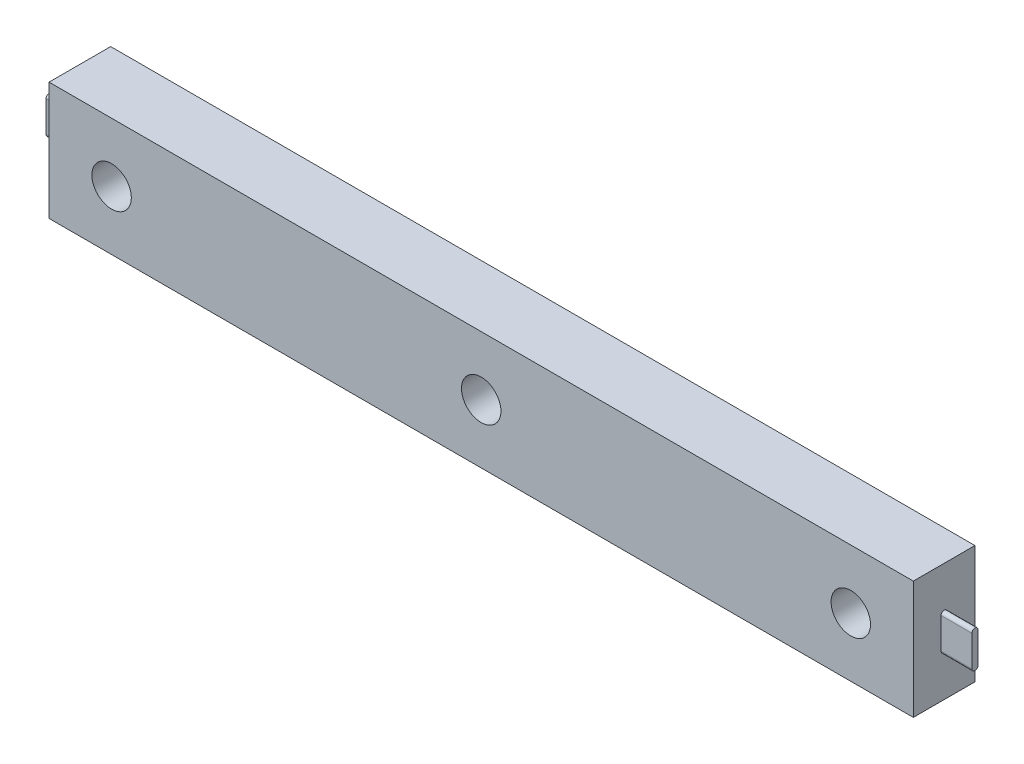
SolidWorks part; units mm, degrees
ref_plane "Front Plane" through (0, 0, 0) normal (0, 0, 1) x (1, 0, 0)
ref_plane "Top Plane" through (0, 0, 0) normal (0, 1, 0) x (1, 0, 0)
ref_plane "Right Plane" through (0, 0, 0) normal (1, 0, 0) x (0, 0, -1)
sketch "Sketch1" plane through (0, 0, 0) normal (0, 0, 1) x (1, 0, 0)
  line L1 (-89.093, -12.1729) -> (89.093, -12.1729)
  line L2 (-89.093, -12.1729) -> (-89.093, 12.1729)
  line L3 (-89.093, 12.1729) -> (89.093, 12.1729)
  line L4 (89.093, -12.1729) -> (89.093, 12.1729)
  line L5 (-89.093, -12.1729) -> (89.093, 12.1729) construction
  line L6 (-89.093, 12.1729) -> (89.093, -12.1729) construction
  circle A0 centre (0, 0) radius 4.064
  circle A1 centre (-76.2, 0) radius 4.064
  circle A2 centre (76.2, 0) radius 4.064
  point P0 (0, 0)
  dimension "D1" = 8.128
  dimension "D2" = 8.128
  dimension "D3" = 8.128
  dimension "D4" = 76.2
  dimension "D5" = 76.2
extrude "Boss-Extrude1" add sketch "Sketch1" along normal blind 12.7 contours L2 L1 L4 L3 | A1 | A0 | A2
sketch "Sketch2" plane through (-89.093, 0, 0) normal (-1, 0, 0) x (0, 0, 1)
  line L3 (5.715, -3.175) -> (5.715, 3.175)
  line L4 (6.985, 3.175) -> (6.985, -3.175)
  arc A1 (6.985, 3.175) -> (5.715, 3.175) centre (6.35, 3.175) ccw
  arc A2 (5.715, -3.175) -> (6.985, -3.175) centre (6.35, -3.175) ccw
  dimension "D2" = 1.27
  dimension "D3" = 1.27
extrude "Boss-Extrude2" add sketch "Sketch2" along normal blind 6.35
sketch "Sketch3" plane through (89.093, 0, 0) normal (1, 0, 0) x (0, 0, -1)
  line L0 (-5.715, 3.175) -> (-5.715, -3.175)
  line L1 (-6.985, -3.175) -> (-6.985, 3.175)
  arc A0 (-5.715, 3.175) -> (-6.985, 3.175) centre (-6.35, 3.175) ccw
  arc A1 (-6.985, -3.175) -> (-5.715, -3.175) centre (-6.35, -3.175) ccw
  dimension "D1" = 1.27
  dimension "D2" = 1.27
extrude "Boss-Extrude3" add sketch "Sketch3" along normal blind 6.35
